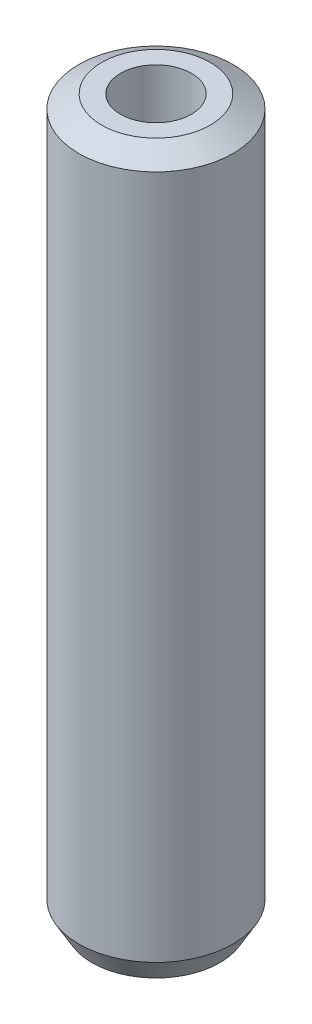
SolidWorks part; units mm, degrees
ref_plane "Front Plane" through (0, 0, 0) normal (0, 0, 1) x (1, 0, 0)
ref_plane "Top Plane" through (0, 0, 0) normal (0, 1, 0) x (1, 0, 0)
ref_plane "Right Plane" through (0, 0, 0) normal (1, 0, 0) x (0, 0, -1)
sketch "Sketch1" plane through (0, 0, 0) normal (0, 1, 0) x (1, 0, 0)
  circle A0 centre (0, 0) radius 7.5
  dimension "SHAFT_OD" = 15
extrude "Boss-Extrude1" add sketch "Sketch1" along normal blind 70.0509
sketch "Sketch2" plane through (0, 0, 0) normal (0, 1, 0) x (1, 0, 0)
  circle A0 centre (0, 0) radius 3.4519
  dimension "BORE_D" = 6.9038
extrude "Cut-Extrude1" cut sketch "Sketch2" along normal through all
chamfer "Chamfer1" distance 1.2802 angle 60 2 edges at (0, 70.0509, 7.5) (0, 0, 7.5) first distance on face at (0, 70.0509, 7.5) first distance on face at (0, 0, 3.4519)
